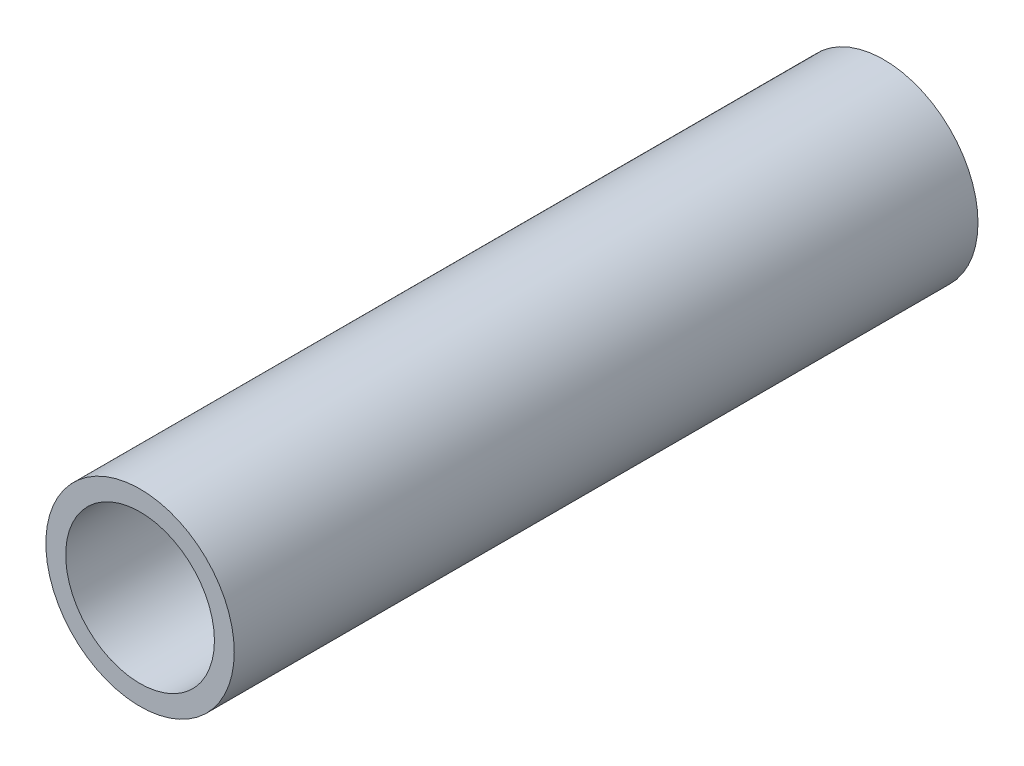
SolidWorks part; units mm, degrees
material "ﾎﾟﾘ塩化ﾋﾞﾆﾙ(PVC)硬質"
ref_plane "正面" through (0, 0, 0) normal (0, 0, 1) x (1, 0, 0)
ref_plane "平面" through (0, 0, 0) normal (0, 1, 0) x (1, 0, 0)
ref_plane "右側面" through (0, 0, 0) normal (1, 0, 0) x (0, 0, -1)
sketch "ｽｹｯﾁ1" plane through (0, 0, 0) normal (0, 0, 1) x (1, 0, 0)
  circle A0 centre (0, 0) radius 19
  circle A1 centre (0, 0) radius 15
  dimension "D1" = 30
  dimension "D2" = 38
extrude "ﾎﾞｽ - 押し出し1" add sketch "ｽｹｯﾁ1" along normal blind 150
